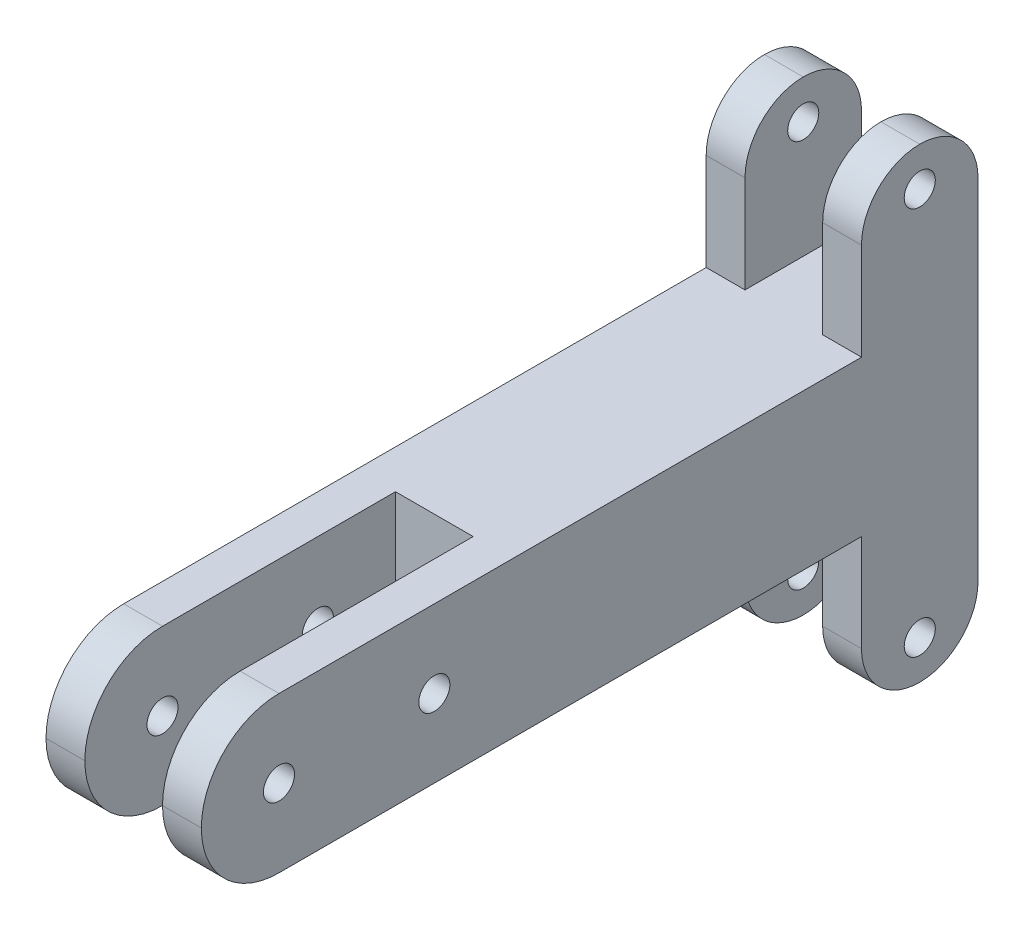
SolidWorks part; units mm, degrees
ref_plane "Front" through (0, 0, 0) normal (0, 0, 1) x (1, 0, 0)
ref_plane "Top" through (0, 0, 0) normal (0, 1, 0) x (1, 0, 0)
ref_plane "Right" through (0, 0, 0) normal (1, 0, 0) x (0, 0, -1)
sketch "Sketch1" plane through (0, 0, 0) normal (0, 1, 0) x (1, 0, 0)
  line L1 (-10, -50) -> (10, -50)
  line L2 (-10, -50) -> (-10, 50)
  line L3 (-10, 50) -> (10, 50)
  line L4 (10, -50) -> (10, 50)
  line L5 (-10, -50) -> (10, 50) construction
  line L6 (-10, 50) -> (10, -50) construction
  point P0 (0, 0)
  dimension "D1" = 20
  dimension "D2" = 100
extrude "Boss-Extrude1" add sketch "Sketch1" along normal blind 20
sketch "Sketch2" plane through (0, 20, 0) normal (0, 1, 0) x (1, 0, 0)
  line L0 (-10, -50) -> (10, -50) construction
  line L1 (-5, -50) -> (5, -50)
  line L2 (-5, -50) -> (-5, -10)
  line L3 (-5, -10) -> (5, -10)
  line L4 (5, -50) -> (5, -10)
  line L5 (-10, 50) -> (-10, -50) construction
  dimension "D1" = 10
  dimension "D2" = 5
  dimension "D3" = 40
extrude "Cut-Extrude1" cut sketch "Sketch2" against normal through all
sketch "Sketch3" plane through (10, 0, 0) normal (1, 0, 0) x (0, 0, -1)
  line L0 (-50, 20) -> (-50, 0) construction
  line L1 (-50, 20) -> (50, 20) construction
  circle A0 centre (-40, 10) radius 2
  circle A1 centre (-20, 10) radius 2
  dimension "D1" = 4
  dimension "D2" = 10
  dimension "D3" = 10
  dimension "D4" = 20
extrude "Cut-Extrude2" cut sketch "Sketch3" against normal through all
fillet "Fillet1" radius 10 4 edges at (7.5, 0, 50) (-7.5, 0, 50) (-7.5, 20, 50) (7.5, 20, 50)
sketch "Sketch4" plane through (0, 20, 0) normal (0, 1, 0) x (1, 0, 0)
  line L0 (10, -40) -> (10, 50) construction
  line L1 (-10, 50) -> (10, 50)
  line L2 (-10, 50) -> (-10, 35)
  line L3 (-10, 35) -> (10, 35)
  line L4 (10, 50) -> (10, 35)
  dimension "D1" = 15
extrude "Boss-Extrude2" add sketch "Sketch4" along normal blind 20
ref_plane "Plane1" through (0, 10, 0) normal (0, 1, 0) x (1, 0, 0)
mirror "Mirror1" about plane through (0, 10, 0) normal (0, 1, 0) of "Boss-Extrude2"
sketch "Sketch5" plane through (-10, 0, 0) normal (-1, 0, 0) x (0, 0, 1)
  line L0 (-50, 40) -> (-35, 40) construction
  line L1 (-50, 40) -> (-50, -20) construction
  line L2 (-50, -20) -> (-35, -20) construction
  circle A0 centre (-42.5, 35) radius 2
  circle A1 centre (-42.5, -15) radius 2
  point P4 (0, 0)
  dimension "D1" = 4
  dimension "D2" = 5
  dimension "D3" = 7.5
  dimension "D4" = 5
extrude "Cut-Extrude3" cut sketch "Sketch5" against normal through all
sketch "Sketch6" plane through (0, 0, -50) normal (0, 0, -1) x (-1, 0, 0)
  line L0 (-10, 40) -> (10, 40) construction
  line L1 (-5, 40) -> (5, 40)
  line L2 (-5, 40) -> (-5, 20)
  line L3 (-5, 20) -> (5, 20)
  line L4 (5, 40) -> (5, 20)
  line L5 (-10, -20) -> (10, -20) construction
  line L6 (-5, -20) -> (5, -20)
  line L7 (-5, -20) -> (-5, 0)
  line L8 (-5, 0) -> (5, 0)
  line L9 (5, -20) -> (5, 0)
  line L10 (-10, 40) -> (-10, -20) construction
  dimension "D1" = 20
  dimension "D2" = 10
  dimension "D3" = 5
extrude "Cut-Extrude4" cut sketch "Sketch6" against normal up to next
fillet "Fillet2" radius 7.5 8 edges at (-7.5, 40, -35) (-7.5, 40, -50) (7.5, 40, -35) (7.5, 40, -50) (7.5, -20, -35) (7.5, -20, -50) (-7.5, -20, -35) (-7.5, -20, -50)
